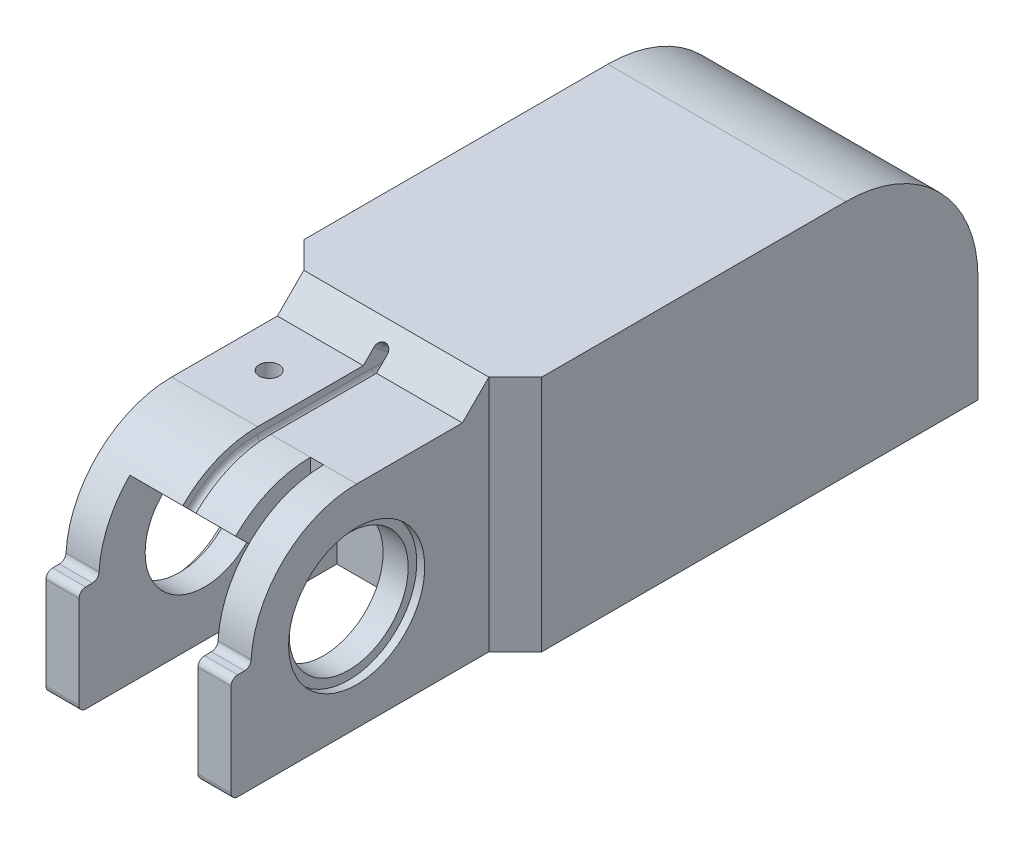
SolidWorks part; units mm, degrees
note: The reader was unsure of these and kept them because the rebuilt part matched: shared geometry of "Esquisse1<3>", "Esquisse1<5>", "Esquisse1<6>".
ref_plane "Plan de face" through (0, 0, 0) normal (0, 0, 1) x (1, 0, 0)
ref_plane "Plan de dessus" through (0, 0, 0) normal (0, 1, 0) x (1, 0, 0)
ref_plane "Plan de droite" through (0, 0, 0) normal (1, 0, 0) x (0, 0, -1)
sketch "Esquisse1" plane through (0, 0, 0) normal (1, 0, 0) x (0, 0, -1)
  line L0 (0, 0) -> (45, 0) construction
  line L1 (0, 0) -> (1.4142, 1.4142)
  line L2 (10, 10) -> (35, 10)
  line L4 (0, 7) -> (10.3452, 7)
  line L5 (10.3452, 7) -> (30.5238, -8)
  line L6 (10, 10) -> (12, 12) construction
  line L9 (32.2, -8) -> (9.6137, 8.7898)
  line L10 (0, 8) -> (8, 8)
  line L11 (0, 5.5) -> (7.3344, 5.5)
  line L12 (7.3344, 5.5) -> (25.4952, -8)
  line L13 (10, 10) -> (10, -8)
  line L14 (13, 10) -> (13, -8)
  line L15 (8, 8) -> (10, 10)
  line L16 (35.2, -8) -> (35.2, -1.65) construction
  line L17 (35.2, -1.65) -> (40, -1.65) construction
  line L18 (40, -1.65) -> (40, -8) construction
  line L19 (37.6, -8) -> (37.6, -1.65) construction
  line L20 (-3.8891, 3.8891) -> (-5.6569, 5.6569)
  line L21 (0, -8) -> (45, -8)
  line L22 (-8, 0) -> (-9.5, 0)
  line L23 (-9.5, 0) -> (-9.5, -8)
  line L24 (-9.5, -8) -> (0, -8)
  line L25 (45, 0) -> (45, -8)
  arc A2 (0, 5.5) -> (-3.8891, 3.8891) centre (0, 0) ccw
  circle A3 centre (0, 0) radius 2
  arc A4 (35, 10) -> (45, 0) centre (35, 0) cw
  arc A5 (9.1716, 9.1716) -> (9.6137, 8.7898) centre (12, 12) ccw
  arc A10 (0, 7) -> (-4.9497, 4.9497) centre (0, 0) ccw
  arc A11 (0, 8) -> (-8, 0) centre (0, 0) ccw
  dimension "D3" = 1.5
  dimension "D4" = 4
  dimension "D8" = 4
  dimension "D11" = 10
  dimension "D15" = 3
  dimension "D16" = 8
  dimension "D20" = 1
  dimension "D5" = 45
  dimension "D6" = 2
  dimension "D7" = 2
  dimension "D9" = 1
  dimension "D10" = 35
  dimension "D12" = 6.35
  dimension "D13" = 3
  dimension "D17" = 4.8
  dimension "D18" = 5
  dimension "D19" = 45
  dimension "D21" = 3
  dimension "D22" = 1.5
extrude "Boss.-Extru.1" add sketch "Esquisse1" along normal blind 2.5 from offset 4.5
extrude "Boss.-Extru.2" add sketch "Esquisse1<3>" along normal blind 2 from surface at 7 starting at face at (7, 2.7071, -1.9179)
sketch "Esquisse1<3>" plane through (0, 0, 0) normal (1, 0, 0) x (0, 0, -1) same geometry as "Esquisse1"
extrude "Boss.-Extru.3" add sketch "Esquisse1<5>" along normal up to surface (6.5 mm away) from offset 0.5 up to face at (7, 0, -2)
sketch "Esquisse1<5>" plane through (0, 0, 0) normal (1, 0, 0) x (0, 0, -1) same geometry as "Esquisse1"
extrude "Boss.-Extru.4" add sketch "Esquisse1<6>" along normal up to surface (7 mm away) up to face at (7, 1.6653, 0.0938)
sketch "Esquisse1<6>" plane through (0, 0, 0) normal (1, 0, 0) x (0, 0, -1) same geometry as "Esquisse1"
fillet "Fillet3" radius 5 1 edges at (0.25, 7, -10.3452)
chamfer "Chamfer1" distance 2 angle 45 2 edges at (7, -3.3558, -13) (9, 1, -10)
fillet "Congé4" radius 0.5 3 edges at (5.75, -8, 9.5) (5.75, 0, 8) (5.75, 0, 9.5)
mirror "Symétrie1" about plane through (0, 0, 0) normal (1, 0, 0) of bodies 118 104
sketch "Esquisse2" plane through (0, 0, 0) normal (0, 0, 1) x (1, 0, 0)
  line L0 (-4.5, -2) -> (-4.5, 2) construction
  circle A3 centre (-3.75, -3.8608) radius 0.75
  dimension "D1" = 1.5
  dimension "D2" = 3.8608
extrude "Enlèv. mat.-Extru.1" [suppressed] cut sketch "Esquisse2" against normal up to next
sketch "Esquisse3" plane through (0, 0, 0) normal (1, 0, 0) x (0, 0, -1)
  line L0 (0, 8) -> (0, -8)
  line L1 (-9, -8) -> (10, -8) construction
  line L2 (0, -8) -> (-8, -8)
  line L3 (-8, -8) -> (-8, 8)
  line L4 (-8, 8) -> (0, 8)
  arc A1 (0, 8) -> (-7.9861, 0.4706) centre (0, 0) ccw construction
extrude "Enlèv. mat.-Extru.2" cut sketch "Esquisse3" against normal blind 1 from surface at 4.5 starting at face at (4.5, 0, -2)
sketch "Esquisse4" plane through (0, -8, 0) normal (0, -1, 0) x (1, 0, 0)
  line L1 (-4, -39) -> (4, -39) construction
  line L2 (9, -45) -> (-9, -45) construction
  circle A0 centre (-4, -39) radius 2.4 construction
  circle A1 centre (4, -39) radius 2.4 construction
  point P2 (0, -39)
  dimension "D1" = 4.8
  dimension "D2" = 6
  dimension "D3" = 8
hole_wizard "Ø4.8 (4.8) Diameter Hole1" positions "Sketch1" profile "Sketch2" hole size "Ø4.8" standard "ANSI Metric"
sketch "Sketch1" plane through (0, -8, 0) normal (0, -1, 0) x (-1, 0, 0)
  point P0 (-4, 39)
  point P3 (4, 39)
sketch "Sketch2" plane through (4, -8, -39) normal (1, 0, 0) x (0, 0, -1)
  line L0 (0, 0) -> (0, 10.4421)
  line L1 (0, 10.4421) -> (2.4, 9)
  line L2 (2.4, 9) -> (2.4, 0)
  line L5 (2.4, 0) -> (0, 0)
  line L10 (0, 10.4421) -> (-2.4, 9) construction
  line L11 (0, -6.35) -> (0, 107.95) construction
  dimension "Hole Dia." = 4.8
  dimension "Hole Depth" = 9
  dimension "Drill Angle" = 118
chamfer "Chamfer2" distance 0.5 angle 45 2 edges at (-4, -8, -41.4) (4, -8, -41.4)
sketch "Esquisse5" plane through (0, 0, 0) normal (1, 0, 0) x (0, 0, -1)
  line L0 (11.2258, 5.4108) -> (12.7173, 7.4172)
  line L1 (12.7173, 7.4172) -> (33.4572, -8)
  line L2 (45, -8) -> (12, -8) construction
  line L3 (33.4572, -8) -> (29.2666, -8)
  line L4 (29.2666, -8) -> (11.2258, 5.4108)
  line L5 (11.6733, 6.0128) -> (30.5238, -8) construction
  line L6 (11.9715, 6.414) -> (31.3619, -8) construction
  line L8 (32.2, -8) -> (9.6137, 8.7898) construction
  dimension "D1" = 0.5
  dimension "D2" = 2.5
extrude "Enlèv. mat.-Extru.4" cut sketch "Esquisse5" against normal mid plane 2.5
fillet "Congé6" radius 5 1 edges at (0, -8, -33.4572)
fillet "Congé1" radius 1.25 6 edges at (1.25, -1.2946, -20.2462) (-1.25, -1.2946, -20.2462) (-1.25, 0.2022, -22.4232) (1.25, 0.2022, -22.4232) (-1.25, -7.7468, -33.541) (1.25, -7.7468, -33.541)
fillet "Congé3" radius 1 1 edges at (0, 1.2884, -13)
fillet "Congé5" radius 0.5 19 edges at (0, 8.7898, -9.6137) (0, 9.1716, -9.1716) (0, 4.9497, 4.9497) (0, 7, 0) (0, 7, -8.6903) (0, 6.0128, -11.6733) (0.5, 6.7468, -10.2614) (-0.5, 7, -4.3452) (-0.5, 8.9726, -9.3856) (-0.5, 6.4672, 2.6788) (-0.5, 6.7468, -10.2614) (-0.5, 7.8026, -10.9418) (-0.5, 6.414, -11.9715) (0.5, 7.8026, -10.9418) (0.5, 6.414, -11.9715) (0, 6.8153, -12.2698) (0.5, 7, -4.3452) (0.5, 6.4672, 2.6788) (0.5, 8.9726, -9.3856)
sketch "Esquisse6" plane through (0, 0, 0) normal (0, 0, 1) x (1, 0, 0)
  line L0 (-7, 0) -> (7, 0)
  line L1 (7, 0) -> (7, 5.15)
  line L2 (7, 5.15) -> (6.4, 5.15)
  line L3 (6.4, 5.15) -> (6.4, 4.5)
  line L4 (6.4, 4.5) -> (-6.4, 4.5)
  line L5 (-6.4, 4.5) -> (-6.4, 5.15)
  line L6 (-6.4, 5.15) -> (-7, 5.15)
  line L7 (-7, 5.15) -> (-7, 0)
  line L8 (7, -0.5) -> (7, -7.5) construction
  line L9 (-7, -0.5) -> (-7, -7.5) construction
  dimension "D1" = 4.5
  dimension "D2" = 5.15
  dimension "D3" = 0.6
revolve "Enlèvement de matière-Révolution1" cut sketch "Esquisse6" angle 360 about L0
sketch "Esquisse7" plane through (9, 0, 0) normal (1, 0, 0) x (0, 0, -1)
  line L0 (0, -4.1275) -> (-15, -4.1275) construction
  line L1 (4.1275, 0) -> (4.1275, 15) construction
  circle A0 centre (0, 0) radius 4.1275 construction
  dimension "D1" = 8.255
  dimension "D2" = 15
sketch "Esquisse8" plane through (0, 8, 0) normal (0, 1, 0) x (1, 0, 0)
  line L0 (7, 4.1275) -> (-7, 4.1275) construction
  line L1 (7, 0) -> (7, 8) construction
  line L2 (-7, 0) -> (-7, 8) construction
  line L3 (-4.5, -4.5) -> (-4.5, 4.5) construction
  circle A0 centre (-3.75, 4.1275) radius 0.75
  dimension "D1" = 1.5
extrude "Enlèv. mat.-Extru.5" cut sketch "Esquisse8" against normal up to next contours A0
